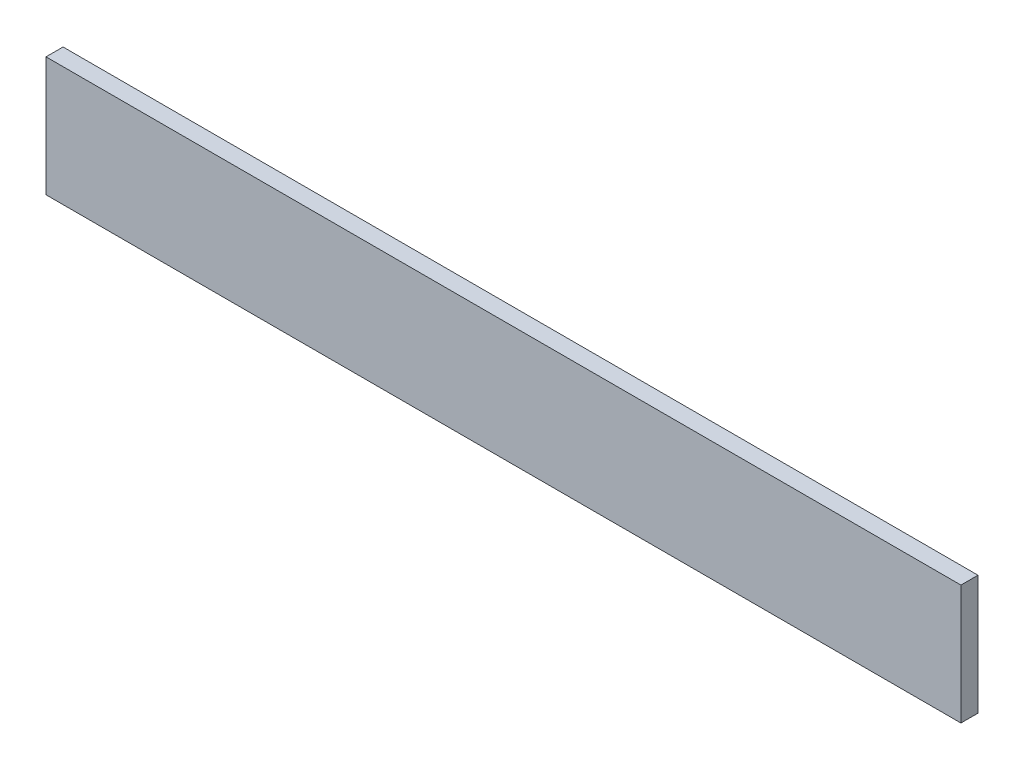
SolidWorks part; units mm, degrees
material "1.4016 (X6Cr17)"
ref_plane "前视基准面" through (0, 0, 0) normal (0, 0, 1) x (1, 0, 0)
ref_plane "上视基准面" through (0, 0, 0) normal (0, 1, 0) x (1, 0, 0)
ref_plane "右视基准面" through (0, 0, 0) normal (1, 0, 0) x (0, 0, -1)
sketch "草图1" plane through (0, 0, 0) normal (0, 0, 1) x (1, 0, 0)
  line L1 (-268, 35) -> (268, 35)
  line L2 (-268, 35) -> (-268, -35)
  line L3 (-268, -35) -> (268, -35)
  line L4 (268, 35) -> (268, -35)
  line L5 (-268, 35) -> (268, -35) construction
  line L6 (-268, -35) -> (268, 35) construction
  point P0 (0, 0)
  dimension "D1" = 70
  dimension "D2" = 536
base flange "基体-法兰1" sketch "草图1" thickness 10 reverse thickness direction no parameters "D1"=4
ref_plane "基准面1" through (0, 0, -5) normal (0, 0, 1) x (1, 0, 0)
sketch "折弯-线1" plane through (0, 0, 0) normal (0, 1, 0) x (1, 0, 0)
sketch "边界框1" plane through (0, 0, 0) normal (0, 1, 0) x (1, 0, 0)
sheet metal parameters "钣金(1)" thickness 10 parameters "D1"=4
flat pattern "平板型式(1)" [suppressed]
sketch "折弯-线2" plane through (0, 0, 0) normal (0, 1, 0) x (1, 0, 0)
sketch "边界框2" [suppressed] plane through (0, 0, 0) normal (0, 1, 0) x (1, 0, 0)
